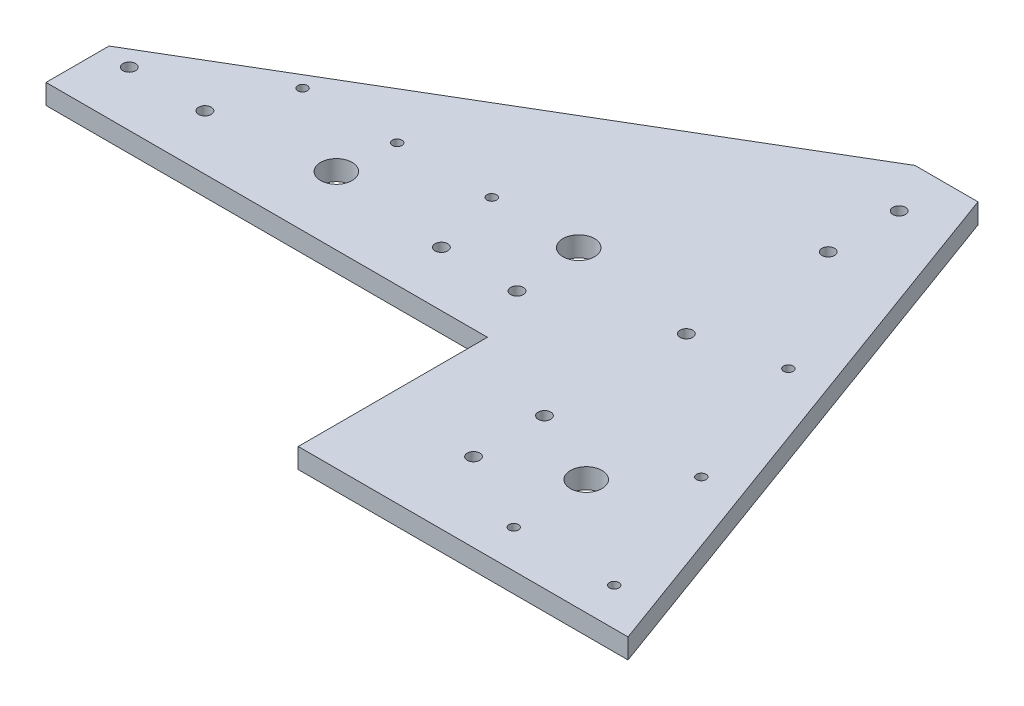
SolidWorks part; units mm, degrees
ref_plane "Front" through (0, 0, 0) normal (0, 0, 1) x (1, 0, 0)
ref_plane "Top" through (0, 0, 0) normal (0, 1, 0) x (1, 0, 0)
ref_plane "Right" through (0, 0, 0) normal (1, 0, 0) x (0, 0, -1)
sketch "Sketch1" plane through (0, 0, 0) normal (0, 1, 0) x (1, 0, 0)
  line L0 (145, 175) -> (180.6, 175)
  line L1 (0, 0) -> (145, 0)
  line L2 (0, 0) -> (0, 175)
  line L3 (0, 175) -> (145, 175)
  line L4 (145, 0) -> (145, 175)
  line L5 (180.6, 175) -> (180.6, 0)
  line L6 (180.6, 0) -> (145, 0)
  line L7 (145, 0) -> (145, 60)
  line L8 (145, 60) -> (140, 60)
  line L9 (140, 60) -> (140, 0)
  line L10 (140, 60) -> (0, 60)
  line L11 (180.6, 175) -> (160.6, 175)
  line L12 (0, 60) -> (0, 80)
  line L13 (160.6, 175) -> (0, 80)
  line L14 (0, 60) -> (70.5, 60)
  line L15 (70.5, 60) -> (70.5, 81.59)
  line L16 (70.5, 81.59) -> (129.875, 81.59)
  line L17 (180.6, 0) -> (244.6, 0)
  line L18 (244.6, 0) -> (180.6, 175)
  line L19 (129.875, 81.59) -> (129.875, 99.09)
  line L20 (244.6, 0) -> (194.75, 0)
  line L21 (194.75, 0) -> (194.75, 36.59)
  circle A0 centre (70.5, 81.59) radius 5
  circle A2 centre (129.875, 99.09) radius 5
  circle A3 centre (194.75, 36.59) radius 5
  dimension "D10" = 59.375
  dimension "D11" = 64
  dimension "D13" = 36.59
  dimension "D1" = 175
  dimension "D2" = 145
  dimension "D3" = 35.6
  dimension "D4" = 60
  dimension "D5" = 5
  dimension "D6" = 20
  dimension "D7" = 20
  dimension "D8" = 70.5
  dimension "D9" = 21.59
  dimension "D12" = 17.5
  dimension "D14" = 49.85
extrude "Boss-Extrude2" add sketch "Sketch1" along normal blind 6.35 contours A2 A0 L10 L8 L4 L13 L2 | L0 L13 L4 L6 L5 | L17 L18 L5 | L8 L9 L1 L4 region at (162.9473, 0, -86.5132) region at (88.7844, 0, -96.4223) region at (202.0355, 0, -58.6426) region at (142.5, 0, -30)
sketch "Sketch3" plane through (0, 6.35, 0) normal (0, 1, 0) x (1, 0, 0)
  line L0 (0, 60) -> (0, 99.0944)
  line L1 (0, 99.0944) -> (42.2796, 99.0944)
  line L2 (42.2796, 99.0944) -> (32.2796, 99.0944)
  line L3 (160.6, 175) -> (0, 80) construction
  line L4 (42.2796, 99.0944) -> (72.2796, 99.0944)
  line L5 (72.2796, 99.0944) -> (102.2796, 99.0944)
  line L6 (102.2796, 99.0944) -> (208.3598, 99.0944)
  line L7 (244.6, 0) -> (180.6, 175) construction
  line L8 (208.3598, 99.0944) -> (196.3598, 99.0944)
  line L9 (244.6, 0) -> (232.0087, 0)
  line L10 (244.6, 0) -> (140, 0) construction
  line L11 (240.2114, 12) -> (228.2114, 12)
  line L12 (228.2114, 12) -> (232.0087, 12)
  line L13 (232.0087, 12) -> (232.0087, 0)
  line L14 (196.3598, 99.0944) -> (228.2114, 12)
  line L15 (228.2114, 12) -> (212.2856, 55.5472)
  line L16 (212.2856, 55.5472) -> (196.3598, 99.0944)
  line L17 (228.2114, 12) -> (196.3598, 12)
  circle A0 centre (42.2796, 99.0944) radius 1.5
  circle A1 centre (72.2796, 99.0944) radius 1.5
  circle A2 centre (102.2796, 99.0944) radius 1.5
  circle A3 centre (196.3598, 99.0944) radius 1.5
  circle A4 centre (212.2856, 55.5472) radius 1.5
  circle A5 centre (228.2114, 12) radius 1.5
  circle A6 centre (196.3598, 12) radius 1.5
  dimension "D5" = 12
  dimension "D6" = 12
  dimension "D1" = 39.0944
  dimension "D2" = 10
  dimension "D3" = 30
  dimension "D4" = 30
  dimension "D7" = 12
extrude "Cut-Extrude1" cut sketch "Sketch3" against normal blind 6.35 contours L2 A0 L4 | L4 A0 L2 | L5 A1 L4 | L4 A1 L5 | A2 | L5 A2 L6 | L6 A3 | L6 A3 | L14 A3 L6 | L14 A4 | L14 A4 | L12 A5 L14 | L14 A5 L17 | L17 A5 L12 | A6 region at (42.2796, 6.35, -99.731) region at (228.7002, 6.35, -12.6992) region at (227.4417, 6.35, -12.5381) region at (212.8835, 6.35, -55.7659) region at (211.6877, 6.35, -55.3285) region at (196.3598, 6.35, -99.731) region at (195.871, 6.35, -98.3952) region at (102.2796, 6.35, -99.731) region at (102.2796, 6.35, -98.4578) region at (72.2796, 6.35, -99.731) region at (72.2796, 6.35, -98.4578) region at (42.2796, 6.35, -98.4578) region at (197.1294, 6.35, -98.5563) region at (228.2114, 6.35, -11.3634)
sketch "Sketch4" plane through (0, 6.35, 0) normal (0, 1, 0) x (1, 0, 0)
  line L0 (170.6, 175) -> (170.6, 137.5)
  line L1 (160.6, 175) -> (180.6, 175) construction
  line L2 (170.6, 137.5) -> (170.6, 92.5)
  line L3 (170.6, 92.5) -> (170.6, 47.5)
  line L4 (170.6, 160) -> (170.6, 25)
  circle A0 centre (170.6, 137.5) radius 2
  circle A1 centre (170.6, 92.5) radius 2
  circle A2 centre (170.6, 47.5) radius 2
  circle A3 centre (170.6, 160) radius 2
  circle A4 centre (170.6, 25) radius 2
  dimension "D4" = 15
  dimension "D1" = 37.5
  dimension "D2" = 45
  dimension "D3" = 45
  dimension "D5" = 135
extrude "Cut-Extrude2" cut sketch "Sketch4" against normal blind 10 contours L0 A3 | L0 A3 | A0 | A1 | A2 | A4 region at (171.4488, 6.35, -160) region at (169.7512, 6.35, -160)
sketch "Sketch6" plane through (0, 0, 0) normal (0, -1, 0) x (-1, 0, 0)
  line L0 (-33, 77.4) -> (-9, 77.4)
  circle A0 centre (-132, 77.4) radius 2
  circle A1 centre (-108, 77.4) radius 2
  circle A2 centre (-33, 77.4) radius 2
  circle A3 centre (-33, 77.4) radius 2
  circle A4 centre (-9, 77.4) radius 2
  dimension "D1" = 24
extrude "Cut-Extrude3" cut sketch "Sketch6" against normal blind 6.35 contours A2 | A4 | A1 | A0
